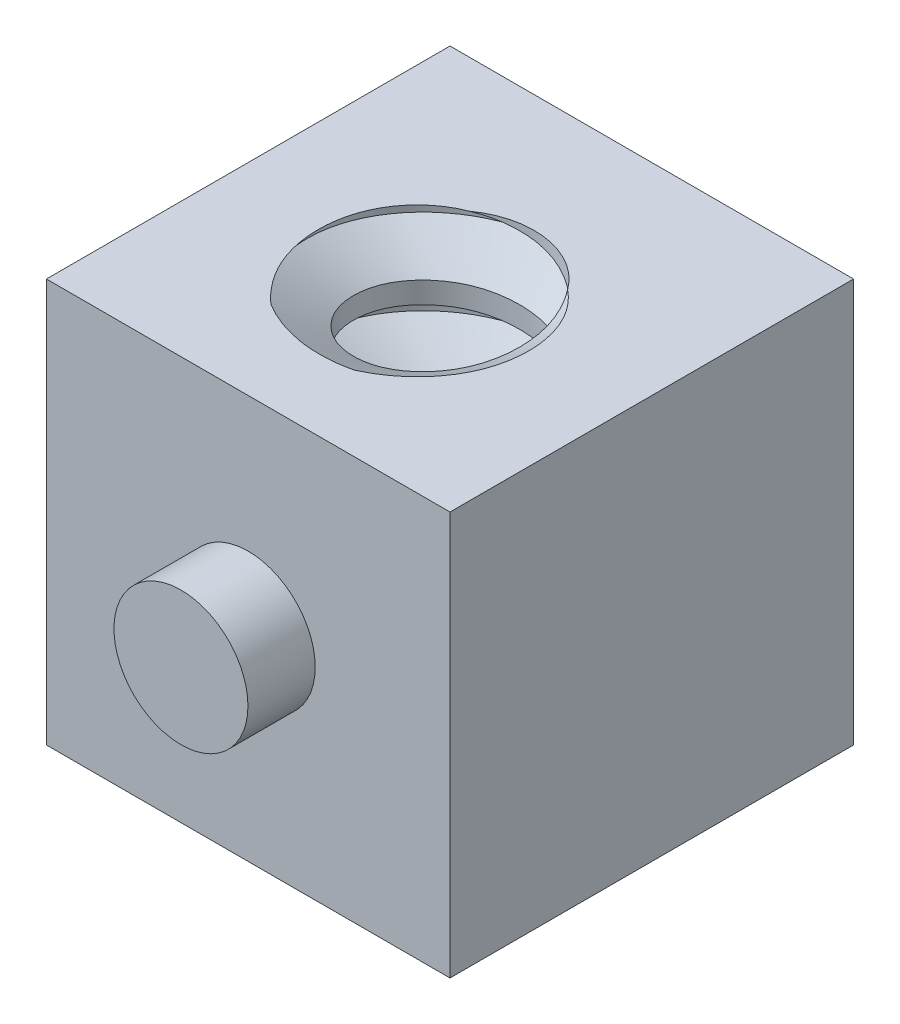
SolidWorks part; units mm, degrees
material "1023 Carbon Steel Sheet (SS)"
ref_plane "Front Plane" through (0, 0, 0) normal (0, 0, 1) x (1, 0, 0)
ref_plane "Top Plane" through (0, 0, 0) normal (0, 1, 0) x (1, 0, 0)
ref_plane "Right Plane" through (0, 0, 0) normal (1, 0, 0) x (0, 0, -1)
sketch "Sketch2" plane through (0, 0, 0) normal (0, 0, 1) x (1, 0, 0)
  circle A0 centre (0, 0) radius 3.75
  dimension "D1" = 7.5
extrude "Boss-Extrude1" add sketch "Sketch2" along normal mid plane 7.5
sketch "Sketch3" plane through (0, 0, 3.75) normal (0, 0, 1) x (1, 0, 0)
  circle A0 centre (0, 0) radius 1.245
  dimension "D1" = 2.49
extrude "Boss-Extrude3" add sketch "Sketch3" along normal blind 1.25 contours A0
mirror "Mirror1" about plane through (0, 0, 0) normal (0, 0, 1) of "Boss-Extrude3"
sketch "Sketch4" plane through (0, 0, 0) normal (0, 1, 0) x (1, 0, 0)
  circle A0 centre (0, 0) radius 1.565
  dimension "D1" = 3.13
extrude "Cut-Extrude2" cut sketch "Sketch4" against normal through all both and the other way through all
sketch "Sketch5" plane through (0, 0, 0) normal (0, 1, 0) x (1, 0, 0)
  point P0 (0, 0)
ref_plane "Plane3" through (0, 3.4, 0) normal (0, 1, 0) x (1, 0, 0)
sketch "Sketch12" plane through (0, 3.4, 0) normal (0, 1, 0) x (1, 0, 0)
  circle A0 centre (0, 0) radius 1.565 construction
  point P0 (1.565, 0)
sketch "Sketch13" plane through (0, 0, -3.75) normal (0, 0, -1) x (-1, 0, 0)
  line L1 (3.75, 3.75) -> (-3.75, 3.75)
  line L2 (3.75, 3.75) -> (3.75, -3.75)
  line L3 (3.75, -3.75) -> (-3.75, -3.75)
  line L4 (-3.75, 3.75) -> (-3.75, -3.75)
  line L5 (3.75, 3.75) -> (-3.75, -3.75) construction
  line L6 (3.75, -3.75) -> (-3.75, 3.75) construction
  circle A0 centre (0, 0) radius 3.75 construction
  point P0 (0, 0)
extrude "Boss-Extrude4" add sketch "Sketch13" against normal up to surface (7.5 mm away) up to face at (1.245, 0, 3.75)
extrude "Cut-Extrude3" cut sketch "Sketch4<3>" against normal through all both and the other way through all
sketch "Sketch4<3>" plane through (0, 0, 0) normal (0, 1, 0) x (1, 0, 0) same geometry as "Sketch4"
thread "Thread2" pitch 1.5875 method cut trim with start face yes trim with end face yes profile "Thread Profile3" start angle 0, offset 5, length 16, pitch 1.5875, diameter 3.13
ref_plane "Plane6" through (-1.565, 8.75, 0) normal (0, 0, 1) x (-1, 0, 0)
sketch "Thread Profile3" plane through (-1.565, 8.75, 0) normal (0, 0, 1) x (-1, 0, 0)
  line L0 (0, 0) -> (0, 1.5875) construction
  line L1 (0, 0) -> (0.8593, 0.4961)
  line L2 (0.8593, 0.4961) -> (0.8593, 0.6945)
  line L3 (0.8593, 0.6945) -> (0, 1.1906)
  line L4 (0.8593, 0.5953) -> (0, 0.5953) construction
  line L11 (0, 0) -> (0, 1.1906)
  point P2 (0, 0)
  dimension "Pitch" = 1.5875
  dimension "Profile_Angle" = 60
  dimension "Profile_Land" = 0.1984
  dimension "Profile_Height" = 0.8593
